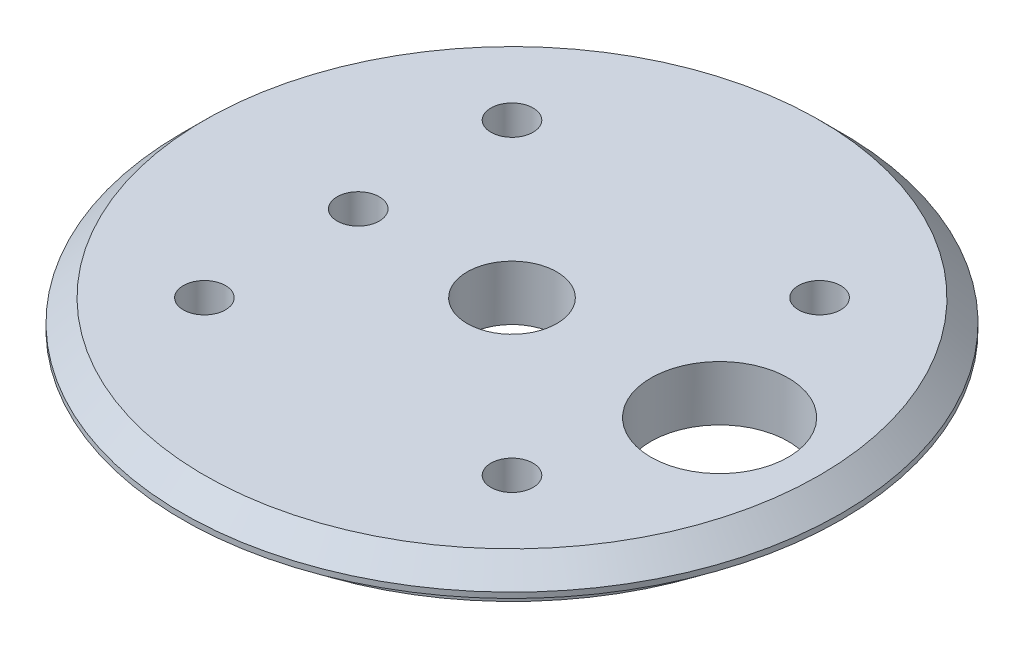
SolidWorks part; units mm, degrees
material "ABS PLASTIC"
ref_plane "Front Plane" through (0, 0, 0) normal (0, 0, 1) x (1, 0, 0)
ref_plane "Top Plane" through (0, 0, 0) normal (0, 1, 0) x (1, 0, 0)
ref_plane "Right Plane" through (0, 0, 0) normal (1, 0, 0) x (0, 0, -1)
sketch "Sketch1" plane through (0, 0, 0) normal (0, 0, 1) x (1, 0, 0)
  line L0 (0, 3.175) -> (19.05, 3.175)
  line L1 (19.05, 3.175) -> (19.05, 1.5875)
  line L2 (19.05, 1.5875) -> (17.018, 1.5875)
  line L3 (17.018, 1.5875) -> (17.018, 0)
  line L4 (17.018, 0) -> (0, 0)
  line L5 (0, 0) -> (0, 3.175)
  line L6 (0, 8.0394) -> (0, -5.1062) construction
  dimension "D1" = 34.036
  dimension "D2" = 38.1
  dimension "D3" = 3.175
  dimension "D4" = 1.5875
revolve "Revolve1" add sketch "Sketch1" angle 360 about L6
hole_wizard "#2 Clearance Hole1" positions "Sketch3" profile "Sketch4" hole size "#2" standard "ANSI Inch" end condition up to next
sketch "Sketch3" plane through (0, 3.175, 0) normal (0, 1, 0) x (1, 0, 0)
  line L1 (-8.89, 8.89) -> (8.89, 8.89)
  line L2 (-8.89, 8.89) -> (-8.89, -8.89)
  line L3 (-8.89, -8.89) -> (8.89, -8.89)
  line L4 (8.89, 8.89) -> (8.89, -8.89)
  point P0 (-8.89, 8.89)
  point P2 (8.89, 8.89)
  point P4 (-8.89, -8.89)
  point P6 (8.89, -8.89)
  point P44 (0, 8.89)
  point P48 (-8.89, 0)
  dimension "D1" = 17.78
  dimension "D2" = 17.78
sketch "Sketch4" plane through (-8.89, 3.175, -8.89) normal (1, 0, 0) x (0, 0, 1)
  line L0 (0, 0) -> (0, 3.175)
  line L1 (0, 3.175) -> (1.2192, 3.175)
  line L2 (1.2192, 3.175) -> (1.2192, 0)
  line L5 (1.2192, 0) -> (0, 0)
  line L11 (0, -6.35) -> (0, 107.95) construction
  dimension "Thru Hole Dia." = 2.4384
  dimension "Thru Hole Depth" = 3.175
hole_wizard "#6 (0.204) Diameter Hole1" positions "Sketch5" profile "Sketch6" hole size "#6" standard "ANSI Inch" end condition up to next
sketch "Sketch5" plane through (0, 3.175, 0) normal (0, 1, 0) x (1, 0, 0)
  point P0 (0, 0)
sketch "Sketch6" plane through (0, 3.175, 0) normal (1, 0, 0) x (0, 0, 1)
  line L0 (0, 0) -> (0, 3.175)
  line L1 (0, 3.175) -> (2.5908, 3.175)
  line L2 (2.5908, 3.175) -> (2.5908, 0)
  line L5 (2.5908, 0) -> (0, 0)
  line L11 (0, -6.35) -> (0, 107.95) construction
  dimension "Thru Hole Dia." = 5.1816
  dimension "Thru Hole Depth" = 3.175
hole_wizard "5/16 (0.3125) Diameter Hole1" positions "Sketch7" profile "Sketch8" hole size "5/16" standard "ANSI Inch" end condition up to next
sketch "Sketch7" plane through (0, 3.175, 0) normal (0, 1, 0) x (1, 0, 0)
  line L0 (-23.8429, 0) -> (23.2099, 0) construction
  point P0 (12, 0)
  dimension "D1" = 12
sketch "Sketch8" plane through (12, 3.175, 0) normal (1, 0, 0) x (0, 0, 1)
  line L0 (0, 0) -> (0, 3.175)
  line L1 (0, 3.175) -> (3.9688, 3.175)
  line L2 (3.9688, 3.175) -> (3.9688, 0)
  line L5 (3.9688, 0) -> (0, 0)
  line L11 (0, -6.35) -> (0, 107.95) construction
  dimension "Thru Hole Dia." = 7.9375
  dimension "Thru Hole Depth" = 3.175
chamfer "Chamfer1" distance 1.27 angle 45 1 edges at (-19.05, 3.175, 0)
